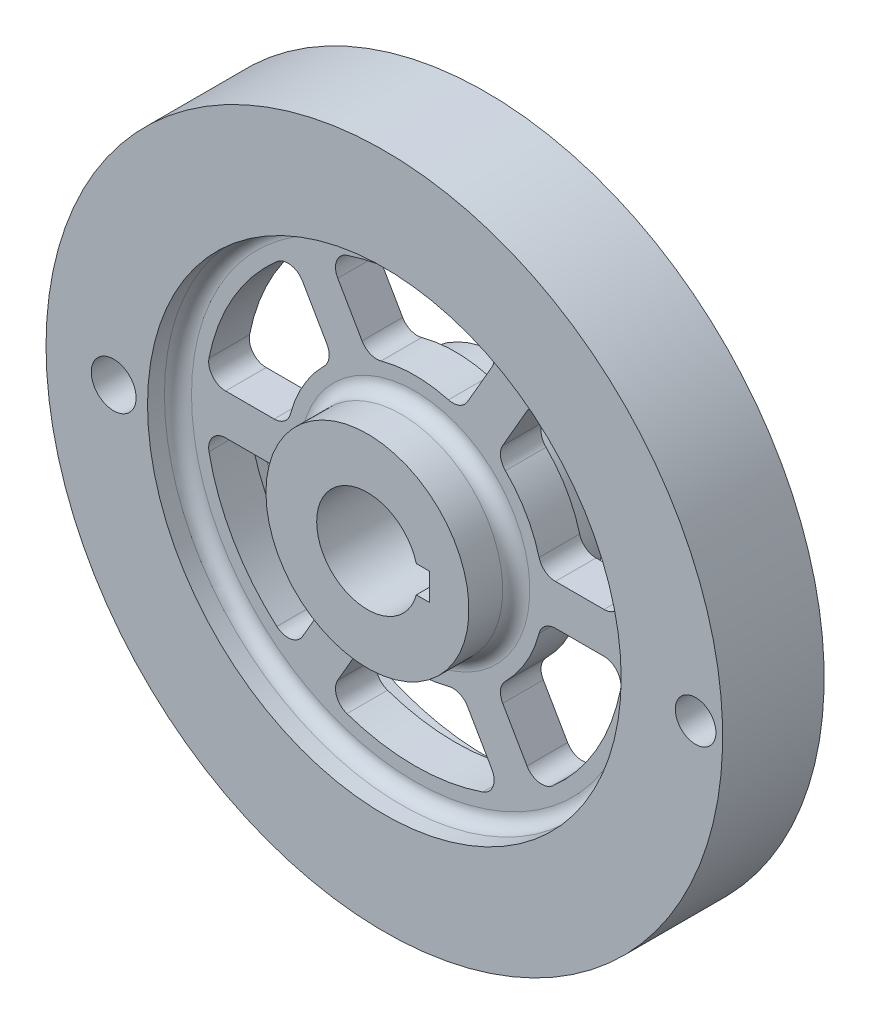
SolidWorks part; units mm, degrees
ref_plane "前视基准面" through (0, 0, 0) normal (0, 0, 1) x (1, 0, 0)
ref_plane "上视基准面" through (0, 0, 0) normal (0, 1, 0) x (1, 0, 0)
ref_plane "右视基准面" through (0, 0, 0) normal (1, 0, 0) x (0, 0, -1)
sketch "草图1" plane through (0, 0, 0) normal (0, 1, 0) x (1, 0, 0)
  line L0 (0, 20) -> (0, -20) construction
  line L1 (15, 20) -> (30, 20)
  line L2 (30, 20) -> (30, 6)
  line L3 (30, 6) -> (70, 6)
  line L4 (70, 6) -> (70, 15)
  line L5 (70, 15) -> (100, 15)
  line L6 (100, 15) -> (100, -15)
  line L7 (100, -15) -> (70, -15)
  line L8 (70, -15) -> (70, -6)
  line L9 (70, -6) -> (30, -6)
  line L10 (30, -6) -> (30, -20)
  line L11 (30, -20) -> (15, -20)
  line L12 (15, -20) -> (15, 20)
revolve "旋转1" add sketch "草图1" angle 360 about L0
fillet "圆角1" radius 4 4 edges at (-70, 0, -6) (-70, 0, 6) (-30, 0, -6) (-30, 0, 6)
ref_axis "基准轴1" through (0, 0, 22) along (0, 0, -1)
sketch "草图4" plane through (0, 0, 0) normal (0, 0, 1) x (1, 0, 0)
  line L0 (41.5692, 6) -> (55.9285, 6)
  line L1 (33.1603, 45.4342) -> (25.9807, 32.9996)
  arc A0 (55.9285, 6) -> (60.8345, 11.9649) centre (55.9285, 11) ccw
  arc A1 (60.8345, 11.9649) -> (40.779, 46.7004) centre (0.0009, -0.0015) ccw
  arc A2 (40.779, 46.7004) -> (33.1603, 45.4342) centre (37.4903, 42.9343) ccw
  arc A3 (25.9807, 32.9996) -> (26.7862, 26.9531) centre (30.3109, 30.4996) ccw
  arc A4 (26.7862, 26.9531) -> (36.7356, 9.7209) centre (-0.0045, -0.0035) cw
  arc A5 (36.7356, 9.7209) -> (41.5692, 6) centre (41.5692, 11) ccw
extrude "切除-拉伸3" cut sketch "草图4" against normal mid plane 12
pattern_circular "阵列(圆周)2" count 6 over 360 about axis through (0, 0, 22) along (0, 0, -1) of "切除-拉伸3"
sketch "草图5" plane through (0, 0, 0) normal (0, 0, 1) x (1, 0, 0)
  line L0 (0, -4) -> (18.3, -4)
  line L1 (18.3, -4) -> (18.3, 4)
  line L2 (18.3, 4) -> (0, 4)
  line L3 (0, 4) -> (0, -4)
extrude "切除-拉伸4" cut sketch "草图5" against normal mid plane 40
ref_plane "基准面1" through (0, 0, 15) normal (0, 0, 1) x (1, 0, 0)
sketch "草图6" plane through (0, 0, 15) normal (0, 0, 1) x (1, 0, 0)
  circle A0 centre (92, 0) radius 6
extrude "切除-拉伸5" cut sketch "草图6" against normal through all
sketch "草图7" plane through (0, 0, 15) normal (0, 0, 1) x (1, 0, 0)
  circle A0 centre (-80, 0) radius 6.6215
extrude "切除-拉伸6" cut sketch "草图7" against normal through all
